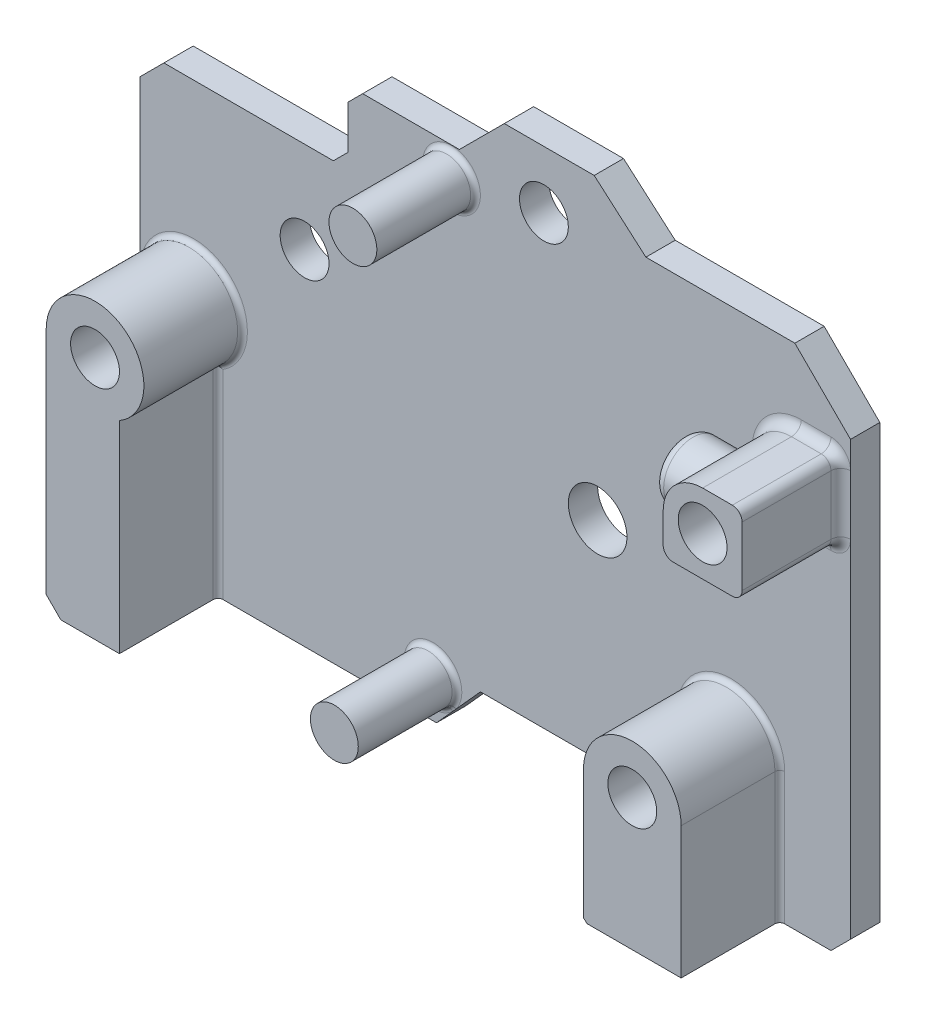
SolidWorks part; units mm, degrees
ref_plane "정면" through (0, 0, 0) normal (0, 0, 1) x (1, 0, 0)
ref_plane "윗면" through (0, 0, 0) normal (0, 1, 0) x (1, 0, 0)
ref_plane "우측면" through (0, 0, 0) normal (1, 0, 0) x (0, 0, -1)
sketch "스케치1" plane through (0, 0, 0) normal (0, 0, 1) x (1, 0, 0)
  line L0 (-6.6755, -27.7059) -> (-2.1735, -22.7059)
  line L1 (0.2695, 28.8941) -> (9.4695, 28.8941)
  line L2 (-42.0305, 9.3941) -> (-42.0305, -27.7059)
  line L3 (-42.0305, -27.7059) -> (-6.6755, -27.7059)
  line L4 (41.6695, 12.6741) -> (41.6695, -27.7059)
  line L5 (-2.1735, -22.7059) -> (13.2865, -22.7059)
  line L6 (13.2865, -22.7059) -> (18.8395, -27.7059)
  line L7 (18.8395, -27.7059) -> (41.6695, -27.7059)
  line L8 (-27.1305, 24.2941) -> (-42.0305, 9.3941)
  line L9 (30.0112, 24.2941) -> (41.6695, 12.6741)
  line L10 (0.2695, 28.8941) -> (-4.3305, 24.2941)
  line L11 (-4.3305, 24.2941) -> (-27.1305, 24.2941)
  line L12 (9.4695, 28.8941) -> (14.7612, 24.2941)
  line L13 (14.7612, 24.2941) -> (30.0112, 24.2941)
  line L14 (14.7612, 24.2941) -> (9.0921, 24.2941) construction
  circle A0 centre (-20.1788, 7.5041) radius 2.5
  circle A1 centre (4.3212, 23.0041) radius 2.5
  circle A2 centre (9.8212, -1.4959) radius 3
  point P0 (0, 0)
  dimension "D3" = 5
  dimension "D6" = 5
  dimension "D7" = 6
  dimension "D4" = 5
  dimension "D2" = 52
  dimension "D5" = 9
  dimension "D8" = 24.5
  dimension "D9" = 15.5
  dimension "D10" = 24.5
  dimension "D11" = 30
  dimension "D12" = 4.6
  dimension "D13" = 9.2
  dimension "D14" = 41
  dimension "D15" = 83.7
  dimension "D16" = 15.25
  dimension "D17" = 37.1
  dimension "D18" = 135
  dimension "D19" = 40.38
  dimension "D20" = 22.8
  dimension "D21" = 135
  dimension "D22" = 15.46
  dimension "D23" = 132
  dimension "D24" = 22.83
  dimension "D25" = 10.44
  dimension "D26" = 5.89
extrude "보스-돌출1" add sketch "스케치1" along normal blind 3
sketch "스케치2" plane through (0, 0, 3) normal (0, 0, 1) x (1, 0, 0)
  line L0 (-42.0305, 9.3941) -> (-42.0305, -27.7059) construction
  line L1 (-42.0305, -27.7059) -> (-6.6755, -27.7059) construction
  line L2 (41.6695, -27.7059) -> (41.6695, 12.6741) construction
  line L3 (18.8395, -27.7059) -> (41.6695, -27.7059) construction
  line L4 (-42.0305, -27.7059) -> (-6.6755, -27.7059) construction
  line L5 (-4.3305, 24.2941) -> (-27.1305, 24.2941) construction
  line L6 (-42.0305, 9.3941) -> (-42.0305, -27.7059) construction
  line L7 (18.4695, -14.2059) -> (18.4695, -27.3728)
  line L8 (13.2865, -22.7059) -> (18.8395, -27.7059) construction
  line L9 (18.4695, -27.3728) -> (18.8395, -27.7059)
  line L10 (18.8395, -27.7059) -> (28.4695, -27.7059)
  line L11 (28.4695, -27.7059) -> (28.4695, -14.2059)
  line L12 (-36.5305, -2.7059) -> (-36.5305, -27.7059)
  line L14 (-29.0305, -27.7059) -> (-36.5305, -27.7059)
  line L15 (-29.0305, -7.0361) -> (-29.0305, -27.7059)
  circle A0 centre (-31.5305, -2.7059) radius 2.5
  arc A2 (28.4695, -14.2059) -> (18.4695, -14.2059) centre (23.4695, -14.2059) ccw
  circle A3 centre (23.4695, -14.2059) radius 2.5
  circle A4 centre (-5.1305, 21.2941) radius 2.45
  circle A5 centre (-7.0305, -23.7059) radius 2.45
  arc A6 (-29.0305, -7.0361) -> (-36.5305, -2.7059) centre (-31.5305, -2.7059) ccw
  dimension "D2" = 5
  dimension "D5" = 10
  dimension "D6" = 5
  dimension "D9" = 4.9
  dimension "D12" = 4.9
  dimension "D3" = 10.5
  dimension "D4" = 25
  dimension "D7" = 18.2
  dimension "D8" = 13.5
  dimension "D10" = 3
  dimension "D11" = 22
  dimension "D13" = 4
  dimension "D14" = 35
  dimension "D15" = 55
  dimension "D16" = 11.5
  dimension "D17" = 26.4
  dimension "D18" = 24
extrude "보스-돌출3" add sketch "스케치2" along normal blind 10.1
extrude "컷-돌출1" cut sketch "스케치2<2>" against normal up to next contours A0 | A3
sketch "스케치2<2>" plane through (0, 0, 3) normal (0, 0, 1) x (1, 0, 0) same geometry as "스케치2"
fillet "필렛1" radius 0.5 8 edges at (23.4695, -9.2059, 3) (-7.5805, 21.2941, 3) (-9.4805, -23.7059, 3) (28.4695, -20.9559, 3) (18.4695, -20.7894, 3) (-29.0305, 1.6242, 3)
sketch "스케치3" plane through (0, 0, 3) normal (0, 0, 1) x (1, 0, 0)
  line L0 (27.6311, 8.7556) -> (33.708, 8.7556)
  line L1 (34.708, 9.7556) -> (34.708, 15.8325)
  line L2 (33.708, 16.8325) -> (30.6695, 16.8325)
  line L3 (26.6311, 9.7556) -> (26.6311, 12.7941)
  line L4 (41.6695, -27.7059) -> (41.6695, 12.6741) construction
  line L6 (28.9695, -27.7059) -> (41.6695, -27.7059) construction
  arc A0 (30.6695, 16.8325) -> (26.6311, 12.7941) centre (30.6695, 12.7941) ccw
  arc A1 (27.6311, 8.7556) -> (26.6311, 9.7556) centre (27.6311, 9.7556) cw
  arc A2 (33.708, 8.7556) -> (34.708, 9.7556) centre (33.708, 9.7556) ccw
  arc A3 (34.708, 15.8325) -> (33.708, 16.8325) centre (33.708, 15.8325) ccw
  dimension "D3" = 1
  dimension "D1" = 11
  dimension "D2" = 40.5
  dimension "D4" = 8.0769
extrude "보스-돌출4" add sketch "스케치3" along normal blind 10.1 contours A0 L3 A1 L0 A2 L1 A3 L2
sketch "스케치4" plane through (26.6311, 0, 0) normal (-1, 0, 0) x (0, 0, 1)
  line L0 (13.1, 12.7941) -> (3, 12.7941) construction
  circle A0 centre (8.05, 12.7941) radius 3
  dimension "D1" = 6
extrude "보스-돌출5" add sketch "스케치4" along normal mid plane 6
fillet "필렛2" radius 1 1 edges at (23.6311, 12.7941, 11.05)
fillet "필렛4" radius 1 8 edges at (32.1888, 16.8325, 3) (34.708, 12.7941, 3) (30.6695, 8.7556, 3) (26.6311, 11.2748, 3) (27.8139, 15.6497, 3) (34.4151, 16.5396, 3) (34.4151, 9.0485, 3) (26.924, 9.0485, 3)
sketch "스케치5" plane through (0, 0, 3) normal (0, 0, 1) x (1, 0, 0)
  line L0 (34.4151, 16.5396) -> (26.924, 9.0485) construction
  circle A4 centre (30.6695, 12.7941) radius 2.5
  arc A5 (34.708, 15.8325) -> (33.708, 16.8325) centre (33.708, 15.8325) ccw construction
  arc A6 (26.6311, 9.7556) -> (27.6311, 8.7556) centre (27.6311, 9.7556) ccw construction
  dimension "D13" = 5
extrude "컷-돌출2" cut sketch "스케치5" against normal mid plane 30 contours A4 L0 | A4 region at (31.4198, 12.0438, 3)
chamfer "모따기1" distance 1 angle 45 2 edges at (41.6695, -27.7059, 1.5) (-42.0305, -27.7059, 1.5)
sketch "스케치6" plane through (0, 0, 13.1) normal (0, 0, 1) x (1, 0, 0)
  point P1 (30.6695, 12.7941)
  point P2 (23.4695, -14.2059)
sketch "스케치8" plane through (0, 0, 3) normal (0, 0, 1) x (1, 0, 0)
  line L0 (-15.7305, 24.2941) -> (-15.7305, 16.8441)
  line L1 (-4.3305, 24.2941) -> (-27.1305, 24.2941) construction
  line L2 (-15.7305, 16.8441) -> (-34.5805, 16.8441)
  line L3 (-27.1305, 24.2941) -> (-42.0305, 9.3941) construction
  line L4 (-34.5805, 16.8441) -> (-27.1305, 24.2941)
  line L5 (-27.1305, 24.2941) -> (-15.7305, 24.2941)
extrude "컷-돌출3" cut sketch "스케치8" against normal up to next and the other way through all
chamfer "모따기2" distance 1.5 angle 45 2 edges at (-15.7305, 24.2941, 1.5) (-15.7305, 16.8441, 1.5)
sketch "스케치10" plane through (0, 0, 3) normal (0, 0, 1) x (1, 0, 0)
  line L0 (41.6695, 12.6741) -> (30.0112, 24.2941) construction
  line L3 (35.708, 18.616) -> (35.708, -27.7059)
  line L5 (35.708, 18.616) -> (41.6695, 12.6741)
  line L6 (41.6695, 12.6741) -> (41.6695, -26.7059)
  line L7 (41.6695, -26.7059) -> (40.6695, -27.7059)
  line L8 (40.6695, -27.7059) -> (35.708, -27.7059)
  line L9 (-37.0305, -2.7059) -> (-37.0305, 14.3941)
  line L10 (28.9695, -27.7059) -> (40.6695, -27.7059) construction
  line L14 (-37.0305, 14.3941) -> (-42.0305, 9.3941)
  line L15 (-42.0305, 9.3941) -> (-42.0305, -26.7059)
  line L16 (-42.0305, -26.7059) -> (-41.0305, -27.7059)
  line L17 (-41.0305, -27.7059) -> (-37.0305, -27.7059)
  line L18 (-37.0305, -2.7059) -> (-37.0305, -27.7059)
  line M11 (33.708, 7.7556) -> (27.6311, 7.7556)
  line M18 (-17.2305, 16.8441) -> (-34.5805, 16.8441)
  line M19 (-34.5805, 16.8441) -> (-42.0305, 9.3941)
  line M20 (-42.0305, 9.3941) -> (-42.0305, -26.7059)
  line M21 (-42.0305, -26.7059) -> (-41.0305, -27.7059)
  line M22 (-41.0305, -27.7059) -> (-37.0305, -27.7059)
  line M30 (28.9695, -14.2059) -> (28.9695, -27.7059)
  line M31 (28.9695, -27.7059) -> (40.6695, -27.7059)
  line M32 (40.6695, -27.7059) -> (41.6695, -26.7059)
  line M33 (41.6695, -26.7059) -> (41.6695, 12.6741)
  line M34 (41.6695, 12.6741) -> (30.0112, 24.2941)
  line M59 (-37.0305, -27.7059) -> (-37.0305, -2.7059)
  dimension "D1" = 5.5
  dimension "D2" = 5.0385
extrude "컷-돌출5" cut sketch "스케치10" against normal up to next contours M18 M19 M20 M21 M22 M59 | M11 M30 M31 M32 M33 M34 region at (38.6154, -5.9551, 3) region at (-39.4722, -7.8303, 3)
chamfer "모따기3" distance 2 angle 45 2 edges at (35.708, -27.7059, 1.5) (-37.0305, -27.7059, 1.5)
sketch "스케치11" plane through (0, -27.7059, 0) normal (0, -1, 0) x (1, 0, 0)
  line L0 (-36.5305, 13.1) -> (-29.0305, 3) construction
  line L2 (18.4695, 13.1) -> (28.4695, 3) construction
  point P12 (23.4695, 8.05)
  point P13 (-32.7805, 8.05)
hole_wizard "M5 나사 구멍2" positions "3D스케치2" profile "스케치13" tap size "M5" standard "KS"
sketch3d "3D스케치2"
  point P0 (23.4695, -27.7059, 8.05)
  point P4 (-32.7805, -27.7059, 8.05)
sketch "스케치13" plane through (23.4695, -27.7059, 8.05) normal (1, 0, 0) x (0, 0, -1)
  line L0 (0, 0) -> (0, 11.2618)
  line L1 (0, 11.2618) -> (2.1, 10)
  line L2 (2.1, 10) -> (2.1, 0)
  line L5 (2.1, 0) -> (0, 0)
  line L10 (0, 11.2618) -> (-2.1, 10) construction
  line L11 (0, -6.35) -> (0, 107.95) construction
  dimension "탭 드릴 지름" = 4.2
  dimension "탭 드릴 깊이" = 10
  dimension "드릴 각도" = 118
cosmetic thread "구멍 나사산3" parameters "D1"=8, "D2"=5
cosmetic thread "구멍 나사산5" parameters "D1"=8, "D2"=5
